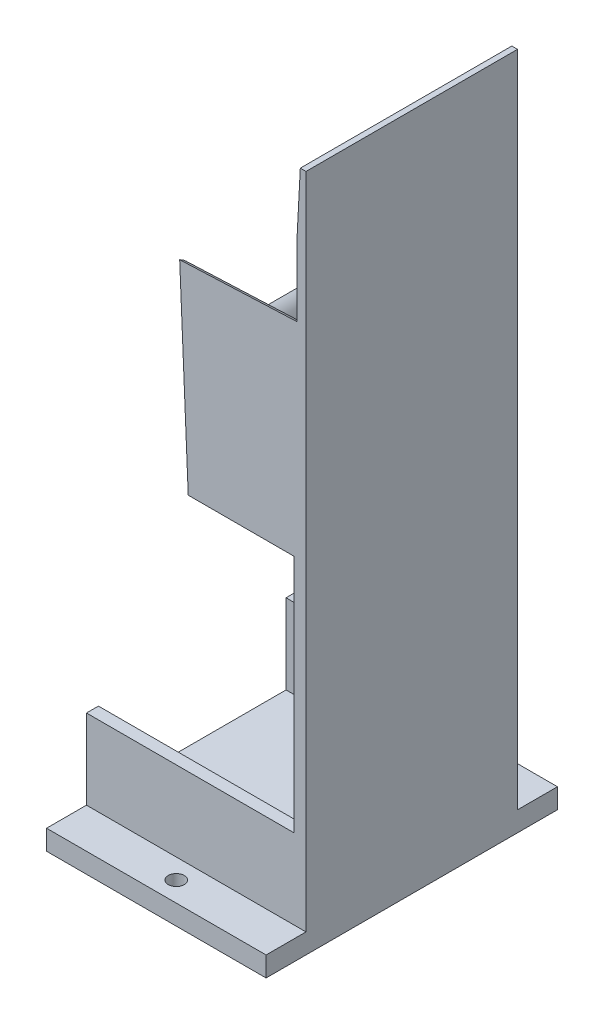
SolidWorks part; units mm, degrees
ref_plane "Front Plane" through (0, 0, 0) normal (0, 0, 1) x (1, 0, 0)
ref_plane "Top Plane" through (0, 0, 0) normal (0, 1, 0) x (1, 0, 0)
ref_plane "Right Plane" through (0, 0, 0) normal (1, 0, 0) x (0, 0, -1)
sketch "Croquis1" plane through (0, 0, 0) normal (0, 1, 0) x (1, 0, 0)
  line L0 (27.5, 26.5) -> (27.5, 36.5)
  line L1 (-27.5, -26.5) -> (27.5, -26.5)
  line L2 (-27.5, -26.5) -> (-27.5, 26.5)
  line L3 (-27.5, 26.5) -> (27.5, 26.5)
  line L4 (27.5, -26.5) -> (27.5, 26.5)
  line L5 (-27.5, -26.5) -> (27.5, 26.5) construction
  line L6 (-27.5, 26.5) -> (27.5, -26.5) construction
  line L7 (-24.3868, -23.5) -> (24.3868, -23.5)
  line L8 (-24.3868, -23.5) -> (-24.3868, 23.5)
  line L9 (-24.3868, 23.5) -> (24.3868, 23.5)
  line L10 (24.3868, -23.5) -> (24.3868, 23.5)
  line L11 (-24.3868, -23.5) -> (24.3868, 23.5) construction
  line L12 (-24.3868, 23.5) -> (24.3868, -23.5) construction
  line L13 (27.5, 36.5) -> (-27.5, 36.5)
  line L14 (-27.5, 36.5) -> (-27.5, 26.5)
  line L15 (0, 0) -> (-15.1383, 0) construction
  line L16 (-27.5, -36.5) -> (-27.5, -26.5)
  line L17 (27.5, -36.5) -> (-27.5, -36.5)
  line L18 (27.5, -26.5) -> (27.5, -36.5)
  circle A0 centre (0, 31.5) radius 2
  circle A1 centre (0, -31.5) radius 2
  point P0 (0, 0)
  point P6 (0, 0)
  point P18 (-27.5, 31.5)
  point P20 (0, 26.5)
  dimension "D4" = 4
  dimension "D1" = 55
  dimension "D2" = 53
  dimension "D3" = 3
  dimension "D5" = 10
extrude "Saliente-Extruir1" add sketch "Croquis1" along normal blind 25 contours L1 L4 L3 L2 L10 L7 L8 L9 region at (26.7362, 0, 0)
sketch "Croquis2" plane through (0, 25, 0) normal (0, 1, 0) x (1, 0, 0)
  line L1 (0, 23.5) -> (0, 26.5)
  line L4 (-27.5, -26.5) -> (27.5, -26.5) construction
  line L6 (0, -26.5) -> (0, -23.5)
  line L12 (0, 26.5) -> (27.5, 26.5)
  line L14 (27.5, 26.5) -> (27.5, -26.5)
  line L15 (27.5, -26.5) -> (0, -26.5)
  line L19 (0, -23.5) -> (24.3868, -23.5)
  line L20 (24.3868, -23.5) -> (24.3868, 23.5)
  line L21 (24.3868, 23.5) -> (0, 23.5)
  line L30 (-24.3868, 23.5) -> (24.3868, 23.5) construction
  line L31 (-27.5, 26.5) -> (27.5, 26.5) construction
  dimension "D1" = 0
  dimension "D2" = 0
  dimension "D3" = 0
extrude "Saliente-Extruir2" add sketch "Croquis2" along normal blind 160
sketch "Croquis3" plane through (0, 0, 23.5) normal (0, 0, -1) x (-1, 0, 0)
  line L5 (0, 155) -> (5, 155)
  line L7 (5, 155) -> (2, 85)
  line L8 (2, 85) -> (0, 85)
  line L12 (0, 185) -> (0, 25) construction
  line L13 (0, 155) -> (0, 85)
  dimension "D1" = 30
  dimension "D2" = 70
  dimension "D3" = 5
  dimension "D4" = 2
extrude "Saliente-Extruir3" add sketch "Croquis3" along normal blind 50 separate body contours L8 L7 L5 region at (-1.8571, 125, 23.5)
extrude "Saliente-Extruir5" add sketch "Croquis3<4>" against normal blind 3
sketch "Croquis3<4>" plane through (0, 0, 23.5) normal (0, 0, -1) x (-1, 0, 0) same geometry as "Croquis3"
sketch "Croquis4" plane through (0, 0, -26.5) normal (0, 0, -1) x (-1, 0, 0)
  line L0 (-24.5, 185) -> (-24.5, 155)
  line L2 (-24.5, 155) -> (75.5, 155)
  line L3 (75.5, 155) -> (75.5, 185)
  line L4 (75.5, 185) -> (-24.5, 185)
  line L5 (-27.5, 185) -> (-27.5, 0) construction
  line L7 (-27.5, 185) -> (0, 185) construction
  dimension "D1" = 3
  dimension "D2" = 100
  dimension "D3" = 30
  dimension "D4" = 30
extrude "Cortar-Extruir1" cut sketch "Croquis4" against normal blind 63
chamfer "Chaflán1" distance 2 angle 88 1 edges at (0, 155, 0) first distance on face at (12.1934, 155, 0)
extrude "Saliente-Extruir6" add sketch "Croquis1<2>" along normal blind 5 contours L1 L4 L3 L2 L10 L7 L8 L9 | L7 L10 L9 L8 region at (26.7362, 0, 0) region at (0, 0, 0)
sketch "Croquis1<2>" plane through (0, 0, 0) normal (0, 1, 0) x (1, 0, 0) same geometry as "Croquis1"
sketch "Croquis5" plane through (0, 0, -26.5) normal (0, 0, -1) x (-1, 0, 0)
  line L0 (5.5, 25) -> (-24.5, 25)
  line L1 (-24.5, 25) -> (-24.5, 85)
  line L2 (-24.5, 85) -> (5.5, 85)
  line L3 (5.5, 85) -> (5.5, 25)
  line L4 (-27.5, 185) -> (-27.5, 0) construction
  line L5 (27.5, 0) -> (-27.5, 0) construction
  dimension "D1" = 3
  dimension "D2" = 60
  dimension "D3" = 30
  dimension "D4" = 25
extrude "Cortar-Extruir2" cut sketch "Croquis5" against normal blind 60
extrude "Saliente-Extruir7" add sketch "Croquis1<4>" along normal blind 5 contours L13 L14 L3 L0 A0 | L18 L1 L16 L17 A1 region at (0, 0, -27.059) region at (26.941, 0, 31.5)
sketch "Croquis1<4>" plane through (0, 0, 0) normal (0, 1, 0) x (1, 0, 0) same geometry as "Croquis1"
sketch "Croquis6" plane through (24.5, 0, 0) normal (-1, 0, 0) x (0, 0, 1)
  line L0 (-26.5, 185) -> (-26.5, 170)
  line L1 (-26.5, 185) -> (-26.5, 155) construction
  line L2 (-26.5, 170) -> (26.5, 170)
  line L3 (26.5, 185) -> (26.5, 155) construction
  line L4 (26.5, 170) -> (26.5, 185)
  line L5 (26.5, 185) -> (-26.5, 185)
extrude "Cortar-Extruir3" cut sketch "Croquis6" against normal blind 5
chamfer "Chaflán2" distance 30 angle 3 1 edges at (24.5, 170, 0) first distance on face at (24.5, 162.5, 0)
chamfer "Chaflán3" distance 5 angle 10 1 edges at (24.3868, 155, 0) first distance on face at (24.3868, 120, 0)
sketch "Croquis7" plane through (-27.5, 0, 0) normal (-1, 0, 0) x (0, 0, 1)
  line L0 (-23.5, 25) -> (23.5, 25)
  line L1 (26.5, 25) -> (-26.5, 25) construction
  line L2 (23.5, 25) -> (23.5, 5)
  line L3 (23.5, 5) -> (-23.5, 5)
  line L4 (-23.5, 5) -> (-23.5, 25)
  line L5 (-26.5, 25) -> (-26.5, 5) construction
  line L6 (26.5, 25) -> (26.5, 5) construction
  line L7 (36.5, 0) -> (-36.5, 0) construction
  dimension "D1" = 3
  dimension "D2" = 3
  dimension "D3" = 5
extrude "Cortar-Extruir4" cut sketch "Croquis7" against normal blind 40
sketch "Croquis8" plane through (1.6398, 0.0703, 0) normal (-0.9991, -0.0428, 0) x (0, 0, 1)
  line L6 (-23.5, 115.0719) -> (23.5, 115.0719)
  line L7 (-23.5, 115.0719) -> (-23.5, 155.0719)
  line L8 (-23.5, 155.0719) -> (23.5, 155.0719)
  line L9 (23.5, 115.0719) -> (23.5, 155.0719)
  line L10 (26.5, 155.0719) -> (-26.5, 155.0719) construction
  line L11 (-26.5, 155.0719) -> (-26.5, 85.0077) construction
  line L12 (26.5, 85.0077) -> (26.5, 155.0719) construction
  dimension "D1" = 3
  dimension "D2" = 3
  dimension "D3" = 40
extrude "Cortar-Extruir5" cut sketch "Croquis8" against normal blind 10
sketch "Croquis9" plane through (0, 0, 26.5) normal (0, 0, 1) x (1, 0, 0)
  line L0 (-5, 155) -> (25.2861, 155)
  line L1 (25.2861, 155) -> (25.2861, 136.2796)
  line L2 (25.2861, 136.2796) -> (-4.1436, 135.0183)
  line L3 (-2, 85) -> (-5, 155) construction
  line L4 (-4.1436, 135.0183) -> (-5, 155)
  dimension "D1" = 20
extrude "Cortar-Extruir6" cut sketch "Croquis9" against normal blind 70
fillet "Redondeo3" radius 5 3 edges at (10.1216, 135.6297, 23.5) (24.3868, 136.2411, 0) (10.1216, 135.6297, -23.5)
fillet "Redondeo5" radius 5 1 edges at (-0.6085, 115.1515, 0)
